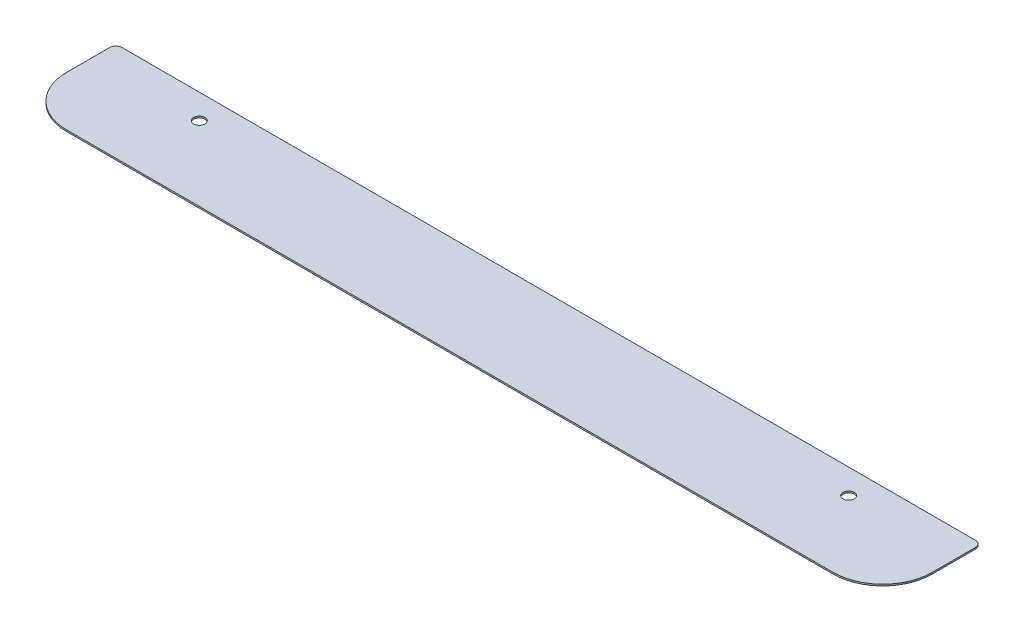
SolidWorks part; units mm, degrees
ref_plane "Front Plane" through (0, 0, 0) normal (0, 0, 1) x (1, 0, 0)
ref_plane "Top Plane" through (0, 0, 0) normal (0, 1, 0) x (1, 0, 0)
ref_plane "Right Plane" through (0, 0, 0) normal (1, 0, 0) x (0, 0, -1)
sketch "Sketch1" plane through (0, 0, 0) normal (0, 1, 0) x (1, 0, 0)
  line L1 (-222.25, -25.4) -> (222.25, -25.4)
  line L2 (-222.25, -25.4) -> (-222.25, 25.4)
  line L3 (-222.25, 25.4) -> (222.25, 25.4)
  line L4 (222.25, -25.4) -> (222.25, 25.4)
  line L5 (-222.25, -25.4) -> (222.25, 25.4) construction
  line L6 (-222.25, 25.4) -> (222.25, -25.4) construction
  point P0 (0, 0)
  dimension "D1" = 444.5
  dimension "D2" = 50.8
extrude "Boss-Extrude1" add sketch "Sketch1" along normal blind 0.7937
fillet "Fillet1" radius 25.4 2 edges at (222.25, 0.3969, 25.4) (-222.25, 0.3969, 25.4)
fillet "Fillet2" radius 3.175 2 edges at (-222.25, 0.3969, -25.4) (222.25, 0.3969, -25.4)
hole_wizard "#1 (0.228) Diameter Hole1" positions "Sketch2" profile "Sketch3" hole size "#1" standard "ANSI Inch" end condition through all
sketch "Sketch2" plane through (0, 0.7937, 0) normal (0, 1, 0) x (1, 0, 0)
  line L0 (-222.25, 12.7) -> (222.25, 12.7) construction
  line L1 (-222.25, 22.225) -> (-222.25, 0) construction
  line L2 (222.25, 0) -> (222.25, 22.225) construction
  line L4 (219.075, 25.4) -> (-219.075, 25.4) construction
  line L5 (0, 12.7) -> (0, 25.4) construction
  point P10 (-166.6875, 12.7)
  point P12 (166.6875, 12.7)
  dimension "D1" = 12.7
  dimension "D2" = 166.6875
  dimension "D3" = 166.6875
sketch "Sketch3" plane through (166.6875, 0.7937, -12.7) normal (1, 0, 0) x (0, 0, 1)
  line L0 (0, 0) -> (0, 0.7937)
  line L1 (0, 0.7937) -> (2.8956, 0.7937)
  line L2 (2.8956, 0.7937) -> (2.8956, 0)
  line L5 (2.8956, 0) -> (0, 0)
  line L11 (0, -6.35) -> (0, 107.95) construction
  dimension "Thru Hole Dia." = 5.7912
  dimension "Thru Hole Depth" = 0.7937
